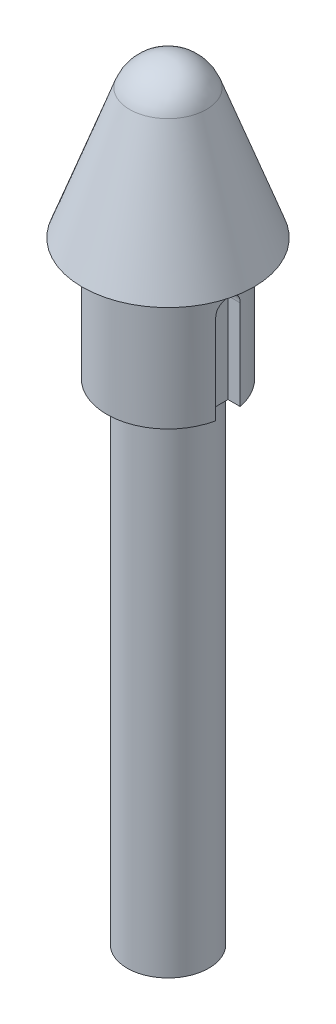
SolidWorks part; units mm, degrees
material "1023 Carbon Steel Sheet (SS)"
ref_plane "Front Plane" through (0, 0, 0) normal (0, 0, 1) x (1, 0, 0)
ref_plane "Top Plane" through (0, 0, 0) normal (0, 1, 0) x (1, 0, 0)
ref_plane "Right Plane" through (0, 0, 0) normal (1, 0, 0) x (0, 0, -1)
ref_axis "Axis1" through (0, -160.1892, 0) along (0, 1, 0)
sketch "Sketch1" plane through (0, 0, 0) normal (0, 0, 1) x (1, 0, 0)
  line L0 (0, -150) -> (15, -150)
  line L1 (0, -55) -> (0, 55) construction
  line L2 (15, -150) -> (15, 0)
  line L3 (15, 0) -> (21, 0)
  line L4 (9.3969, 31.8792) -> (21, 0)
  line L5 (0, 38.459) -> (0, -150)
  line L6 (0, 38.459) -> (46.473, 38.459) construction
  arc A0 (0, 38.459) -> (9.3969, 31.8792) centre (0, 28.459) cw
  dimension "D5" = 10
  dimension "D1" = 20
  dimension "D2" = 15
  dimension "D3" = 150
  dimension "D4" = 21
revolve "Revolve1" add sketch "Sketch1" angle 360 about axis through (0, -160.1892, 0) along (0, 1, 0)
sketch "Sketch2" plane through (0, 0, 0) normal (0, 0, 1) x (1, 0, 0)
  line L0 (15, -150) -> (15, 0) construction
  line L1 (15, -30) -> (10, -30)
  line L2 (15, -30) -> (15, -150)
  line L3 (15, -150) -> (10, -150)
  line L4 (10, -30) -> (10, -150)
  line L5 (-15, -150) -> (15, -150) construction
  line L6 (0, 9.4212) -> (0, -39.2525) construction
  line L7 (0, -160.1892) -> (0, 55) construction
  line L9 (23.1, 0) -> (-23.1, 0) construction
  dimension "D1" = 20
  dimension "D2" = 30
revolve "Cut-Revolve1" cut sketch "Sketch2" angle 360 about L6
sketch "Sketch3" plane through (0, -30, 0) normal (0, -1, 0) x (1, 0, 0)
  line L0 (14.6969, 3) -> (11.6969, 3)
  line L1 (11.6969, 3) -> (11.6969, -3)
  line L2 (11.6969, -3) -> (14.6969, -3)
  line L3 (15.8522, 0) -> (10.4119, 0) construction
  arc A0 (14.6969, 3) -> (14.6969, -3) centre (0, 0) cw
  circle A1 centre (0, 0) radius 15 construction
  point P9 (0, 0)
  dimension "D1" = 3
  dimension "D2" = 6
extrude "Cut-Extrude1" cut sketch "Sketch3" against normal blind 25
fillet "Fillet1" radius 3 2 edges at (13.1969, -5, 3) (13.1969, -5, -3)
